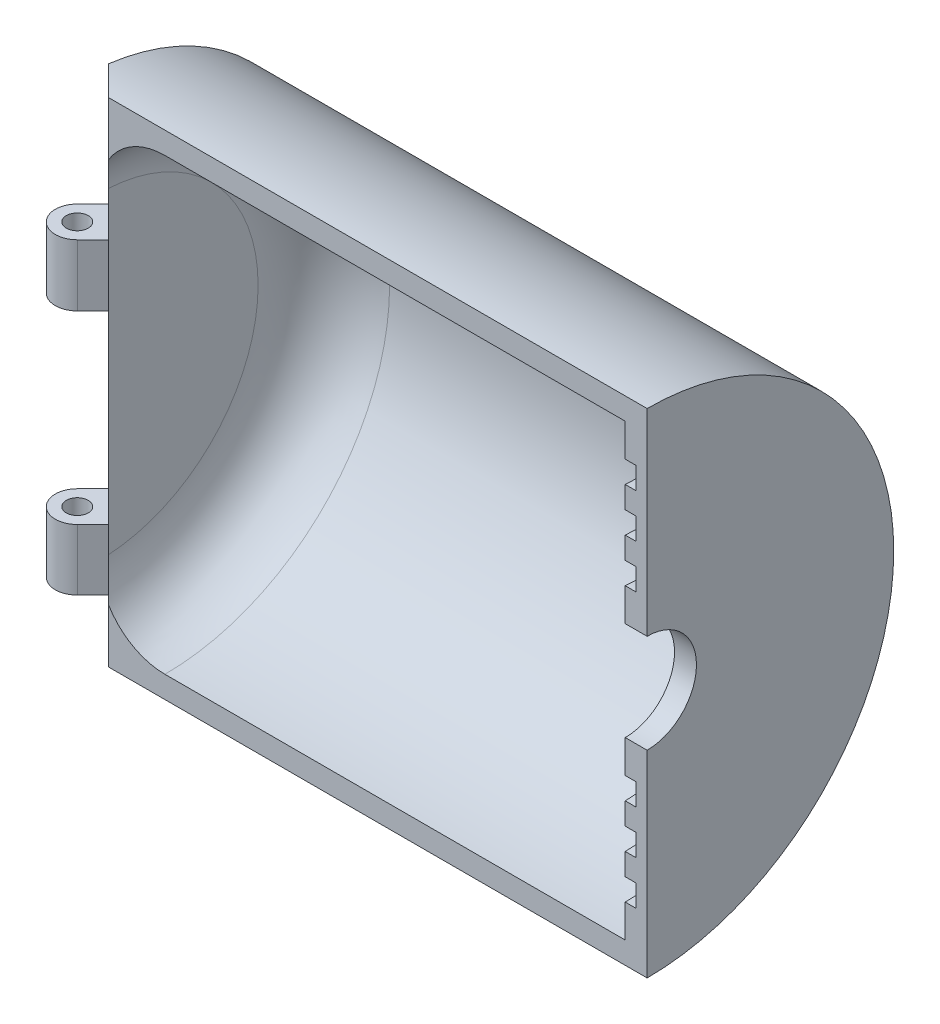
SolidWorks part; units mm, degrees
ref_plane "Front Plane" through (0, 0, 0) normal (0, 0, 1) x (1, 0, 0)
ref_plane "Top Plane" through (0, 0, 0) normal (0, 1, 0) x (1, 0, 0)
ref_plane "Right Plane" through (0, 0, 0) normal (1, 0, 0) x (0, 0, -1)
sketch "Sketch1" plane through (0, 0, 0) normal (1, 0, 0) x (0, 0, -1)
  line L0 (0, -10.25) -> (0, 10.25)
  arc A0 (0, -10.25) -> (0, 10.25) centre (0, 0) ccw
  circle A2 centre (0, 0) radius 2.25
extrude "Boss-Extrude1" add sketch "Sketch1" along normal blind 1 contours A2 L0 A0 region at (0, 0, -4.5221)
sketch "Sketch2" plane through (0, 0, 0) normal (-1, 0, 0) x (0, 0, 1)
  circle A0 centre (0, 0) radius 4.25 construction
  circle A2 centre (0, 0) radius 6.25 construction
  circle A3 centre (0, 0) radius 8.25 construction
  arc A4 (0, 2.25) -> (0, -2.25) centre (0, 0) ccw construction
  circle A5 centre (0, 0) radius 3.75
  circle A6 centre (0, 0) radius 4.75
  circle A7 centre (0, 0) radius 5.75
  circle A8 centre (0, 0) radius 6.75
  circle A9 centre (0, 0) radius 7.75
  circle A10 centre (0, 0) radius 8.75
  line M11 (0, 2.25) -> (0, 10.25)
  line M13 (0, -10.25) -> (0, -2.25)
  dimension "D1" = 2
  dimension "D2" = 4
  dimension "D3" = 6
  dimension "D4" = 0.5
  dimension "D5" = 0.5
  dimension "D6" = 0.5
  dimension "D7" = 0.5
  dimension "D8" = 0.5
  dimension "D9" = 0.5
extrude "Cut-Extrude1" cut sketch "Sketch2" against normal blind 0.5 contours A6 A5 M11 M13 | A8 A7 M11 M13 | A10 A9 M11 M13 region at (0, 0, -3.8562) region at (0, 0, -5.9009) region at (0, 0, -7.9457)
sketch "Sketch3" plane through (1, 0, 0) normal (1, 0, 0) x (0, 0, -1)
  line L0 (0, -10.25) -> (0, -11.25)
  line L1 (0, 10.25) -> (0, 11.25)
  arc A0 (0, -11.25) -> (0, 11.25) centre (0, 0) ccw
  arc A2 (0, -10.25) -> (0, 10.25) centre (0, 0) ccw construction
  arc A3 (0, -10.25) -> (0, 10.25) centre (0, 0) ccw
  dimension "D1" = 1
extrude "Boss-Extrude2" add sketch "Sketch3" against normal blind 25
sketch "Sketch6" plane through (-24, 0, 0) normal (-1, 0, 0) x (0, 0, 1)
  line L0 (0, 11.25) -> (0, -11.25)
  arc A0 (0, 11.25) -> (0, -11.25) centre (0, 0) ccw construction
  arc A1 (0, 11.25) -> (0, -11.25) centre (0, 0) ccw
extrude "Boss-Extrude3" add sketch "Sketch6" along normal blind 1
ref_plane "Plane3" through (0, 11.25, 0) normal (0, 1, 0) x (1, 0, 0)
sketch "Sketch7" plane through (0, 11.25, 0) normal (0, 1, 0) x (1, 0, 0)
  line L0 (-23.5858, 0) -> (-25, 1.4142)
  line L1 (-25, 0) -> (1, 0) construction
  line L2 (-25, 11.25) -> (-25, 0) construction
  line L3 (-25, 1.4142) -> (-25.7071, 0.7071)
  line L5 (-24.2929, -0.7071) -> (-23.5858, 0)
  arc A0 (-25.7071, 0.7071) -> (-24.2929, -0.7071) centre (-25, 0) ccw
  circle A1 centre (-25, 0) radius 0.5
  point P10 (0, 0)
  point P11 (-20, 0)
  point P12 (-25, 0)
  dimension "D4" = 1
  dimension "D1" = 45
  dimension "D2" = 2
extrude "Boss-Extrude4" add sketch "Sketch7" against normal blind 22.5
sketch "Sketch10" plane through (0, 11.25, 0) normal (0, 1, 0) x (1, 0, 0)
  circle A0 centre (-25, 0) radius 0.5
extrude "Cut-Extrude4" cut sketch "Sketch10" against normal blind 40.5
sketch "Sketch8" plane through (-11.7929, 0, -11.7929) normal (0.7071, 0, 0.7071) x (0.7071, 0, -0.7071)
  line L1 (-16.6777, 11.25) -> (-27.5457, 11.25)
  line L2 (-16.6777, 11.25) -> (-16.6777, 5.625)
  line L3 (-16.6777, 5.625) -> (-27.5457, 5.625)
  line L4 (-27.5457, 11.25) -> (-27.5457, 5.625)
  line L6 (-17.6777, 11.25) -> (-16.6777, 11.25) construction
  line L7 (-16.6777, -10.25) -> (-16.6777, 10.25) construction
  dimension "D2" = 5.625
extrude "Cut-Extrude2" cut sketch "Sketch8" against normal blind 22.5
pattern_linear "LPattern1" count 2 spacing 11.25 along (0, -1, 0) of "Cut-Extrude2"
sketch "Sketch9" plane through (1, 0, 0) normal (1, 0, 0) x (0, 0, -1)
  circle A0 centre (0, 0) radius 11.25
  circle A1 centre (0, 0) radius 20.4737
extrude "Cut-Extrude3" cut sketch "Sketch9" against normal blind 40.5
sketch "Sketch11" plane through (-11.7929, 0, -11.7929) normal (0.7071, 0, 0.7071) x (0.7071, 0, -0.7071)
  line L0 (-16.6777, -10.25) -> (-16.6777, -5.625) construction
  line L1 (-16.6777, -0.7716) -> (-23.403, -0.7716)
  line L2 (-16.6777, -0.7716) -> (-16.6777, 2.8125)
  line L3 (-16.6777, 2.8125) -> (-23.403, 2.8125)
  line L4 (-23.403, -0.7716) -> (-23.403, 2.8125)
  line L5 (-16.6777, -12.0344) -> (-23.9068, -12.0344)
  line L6 (-16.6777, -12.0344) -> (-16.6777, -8.4149)
  line L7 (-16.6777, -8.4149) -> (-23.9068, -8.4149)
  line L8 (-23.9068, -12.0344) -> (-23.9068, -8.4149)
  point P4 (-13.1421, -8.4149)
extrude "Cut-Extrude5" cut sketch "Sketch11" against normal blind 40.5
fillet "Fillet1" radius 3 1 edges at (-24, 0, -10.25)
